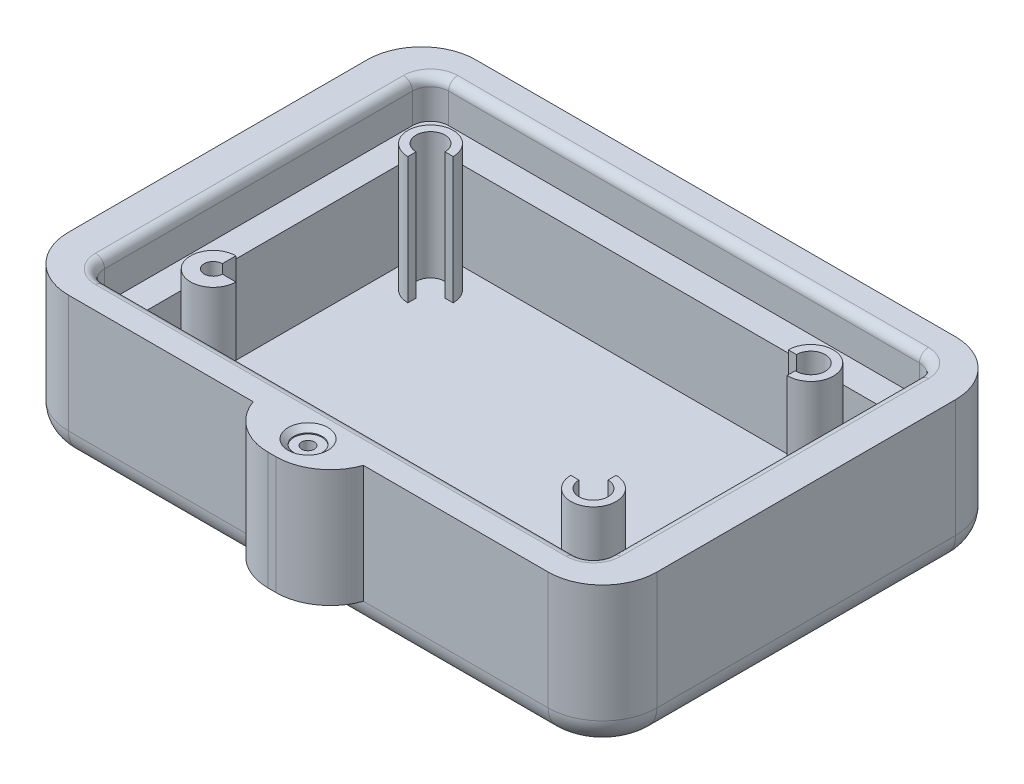
SolidWorks part; units mm, degrees
ref_plane "Front Plane" through (0, 0, 0) normal (0, 0, 1) x (1, 0, 0)
ref_plane "Top Plane" through (0, 0, 0) normal (0, 1, 0) x (1, 0, 0)
ref_plane "Right Plane" through (0, 0, 0) normal (1, 0, 0) x (0, 0, -1)
sketch "Sketch1" plane through (0, 0, 0) normal (0, 1, 0) x (1, 0, 0)
  line L1 (0, 0) -> (82.55, 0)
  line L2 (0, 0) -> (0, 57.15)
  line L3 (0, 57.15) -> (82.55, 57.15)
  line L4 (82.55, 0) -> (82.55, 57.15)
  dimension "D1" = 57.15
  dimension "D2" = 82.55
extrude "Boss-Extrude1" add sketch "Sketch1" along normal blind 20.32
fillet "Fillet2" radius 7.62 4 edges at (82.55, 10.16, -57.15) (82.55, 10.16, 0) (0, 10.16, 0) (0, 10.16, -57.15)
fillet "Fillet3" radius 3.81 8 edges at (80.3182, 0, -54.9182) (82.55, 0, -28.575) (80.3182, 0, -2.2318) (41.275, 0, 0) (2.2318, 0, -2.2318) (0, 0, -28.575) (2.2318, 0, -54.9182) (41.275, 0, -57.15)
sketch "Sketch2" plane through (0, 20.32, 0) normal (0, 1, 0) x (1, 0, 0)
  line L0 (0, 28.575) -> (82.55, 28.575) construction
  line L1 (0, 49.53) -> (0, 7.62) construction
  line L2 (82.55, 7.62) -> (82.55, 49.53) construction
  line L4 (9.525, 8.255) -> (73.025, 8.255)
  line L5 (9.525, 8.255) -> (9.525, 48.895)
  line L6 (9.525, 48.895) -> (73.025, 48.895)
  line L7 (73.025, 8.255) -> (73.025, 48.895)
  line L8 (9.525, 8.255) -> (73.025, 48.895) construction
  line L9 (9.525, 48.895) -> (73.025, 8.255) construction
  point P6 (41.275, 28.575)
  dimension "D1" = 40.64
  dimension "D2" = 63.5
extrude "Cut-Extrude1" cut sketch "Sketch2" against normal blind 17.78
sketch "Sketch7" plane through (0, 20.32, 0) normal (0, 1, 0) x (1, 0, 0)
  line L14 (5.715, 52.705) -> (5.715, 4.445)
  line L15 (5.715, 4.445) -> (76.835, 4.445)
  line L16 (76.835, 4.445) -> (76.835, 52.705)
  line L17 (76.835, 52.705) -> (5.715, 52.705)
  line L18 (5.715, 52.705) -> (5.715, 4.445)
  line L19 (5.715, 4.445) -> (76.835, 4.445)
  line L20 (76.835, 4.445) -> (76.835, 52.705)
  line L21 (76.835, 52.705) -> (5.715, 52.705)
  dimension "D1" = 3.81
sketch "Sketch5" plane through (0, 2.54, 0) normal (0, 1, 0) x (1, 0, 0)
  line L0 (9.525, 48.895) -> (9.525, 8.255) construction
  line L2 (73.025, 48.895) -> (9.525, 48.895) construction
  line L3 (9.525, 8.255) -> (73.025, 8.255) construction
  line L4 (73.025, 8.255) -> (73.025, 48.895) construction
  circle A0 centre (14.605, 43.815) radius 3.175
  circle A1 centre (14.605, 13.335) radius 3.175
  circle A2 centre (67.945, 43.815) radius 3.175
  circle A3 centre (67.945, 13.335) radius 3.175
  point P16 (0, 0)
  point P18 (67.056, 8.2679)
  dimension "D5" = 6.35
  dimension "D6" = 6.35
  dimension "D7" = 6.35
  dimension "D8" = 6.35
  dimension "D11" = 5.08
  dimension "D1" = 5.08
  dimension "D2" = 5.08
  dimension "D3" = 5.08
  dimension "D4" = 5.08
  dimension "D9" = 5.08
  dimension "D10" = 5.08
  dimension "D12" = 5.08
sketch "Sketch9" plane through (0, 0, 0) normal (0, 0, 1) x (1, 0, 0)
  line L0 (41.275, 20.32) -> (41.275, 3.81) construction
  line L1 (7.62, 20.32) -> (74.93, 20.32) construction
  line L2 (7.62, 3.81) -> (74.93, 3.81) construction
  line L4 (49.0058, 20.32) -> (33.5442, 20.32)
  line L5 (49.0058, 20.32) -> (49.0058, 3.81)
  line L6 (49.0058, 3.81) -> (33.5442, 3.81)
  line L7 (33.5442, 20.32) -> (33.5442, 3.81)
  line L8 (49.0058, 20.32) -> (33.5442, 3.81) construction
  line L9 (49.0058, 3.81) -> (33.5442, 20.32) construction
  point P6 (41.275, 12.065)
extrude "Boss-Extrude5" add sketch "Sketch9" along normal blind 5.08
fillet "Fillet10" radius 7.62 2 edges at (49.0058, 12.065, 5.08) (33.5442, 12.065, 5.08)
extrude "Cut-Extrude4" cut sketch "Sketch7" against normal blind 5.461
fillet "Fillet12" radius 2.54 4 edges at (76.835, 17.5895, -52.705) (76.835, 17.5895, -4.445) (5.715, 17.5895, -52.705) (5.715, 17.5895, -4.445)
fillet "Fillet13" radius 1.27 8 edges at (6.4589, 20.32, -5.1889) (5.715, 20.32, -28.575) (6.4589, 20.32, -51.9611) (41.275, 20.32, -52.705) (76.0911, 20.32, -51.9611) (76.835, 20.32, -28.575) (76.0911, 20.32, -5.1889) (41.275, 20.32, -4.445)
extrude "Boss-Extrude6" add sketch "Sketch5" along normal blind 17.78
sketch "Sketch11" plane through (0, 20.32, 0) normal (0, 1, 0) x (1, 0, 0)
  circle A0 centre (14.605, 13.335) radius 1.27
  circle A1 centre (14.605, 43.815) radius 2.032
  circle A2 centre (67.945, 13.335) radius 2.032
  circle A3 centre (67.945, 43.815) radius 2.032
  dimension "D1" = 2.54
  dimension "D2" = 4.064
  dimension "D3" = 4.064
  dimension "D4" = 4.064
extrude "Cut-Extrude5" cut sketch "Sketch11" against normal blind 17.78
sketch "Sketch17" plane through (0, 2.54, 0) normal (0, 1, 0) x (1, 0, 0)
  arc A0 (67.8016, 40.6432) -> (64.6138, 43.8311) centre (67.8016, 43.8311) cw
  circle A1 centre (67.945, 43.815) radius 3.175 construction
  arc A2 (64.77, 13.335) -> (67.945, 16.51) centre (67.945, 13.335) cw
  circle A3 centre (67.945, 13.335) radius 3.175 construction
  circle A4 centre (67.945, 13.335) radius 3.175 construction
  arc A5 (17.78, 43.815) -> (14.605, 40.64) centre (14.605, 43.815) cw
  circle A6 centre (14.605, 43.815) radius 3.175 construction
  circle A7 centre (14.605, 43.815) radius 3.175 construction
  arc A8 (14.605, 16.51) -> (17.78, 13.335) centre (14.605, 13.335) cw
  circle A9 centre (14.605, 13.335) radius 3.175 construction
  circle A10 centre (14.605, 13.335) radius 3.175 construction
extrude "Cut-Extrude-Thin1" cut sketch "Sketch17" along normal through all thin thin type one direction wall 2.54
hole_wizard "CBORE for #0 Binding Head Machine Screw1" positions "Sketch20" profile "Sketch19" counterbore size "#0" standard "ANSI Inch" end condition through all
sketch "Sketch20" plane through (0, 20.32, 0) normal (0, 1, 0) x (1, 0, 0)
  point P0 (41.9111, -0.6748)
sketch "Sketch19" plane through (41.9111, 20.32, 0.6748) normal (1, 0, 0) x (0, 0, 1)
  line L0 (0, 0) -> (0, 20.32)
  line L1 (0, 20.32) -> (0.889, 20.32)
  line L3 (0.889, 20.32) -> (0.889, 0.8128)
  line L4 (1.985, 0.8128) -> (0.889, 0.8128)
  line L5 (1.985, 0.8128) -> (1.985, 0.6682)
  line L6 (1.985, 0.6682) -> (2.7813, 0)
  line L7 (2.7813, 0) -> (0, 0)
  line L8 (-1.985, 0.6682) -> (-2.7813, 0) construction
  line L11 (0, -6.35) -> (0, 107.95) construction
  dimension "Thru Hole Dia." = 1.778
  dimension "Thru Hole Depth" = 20.32
  dimension "C'Bore Dia." = 3.97
  dimension "C'Bore Depth" = 0.8128
  dimension "Near C'Sink Dia." = 5.5626
  dimension "Near C'Sink Angle" = 100
